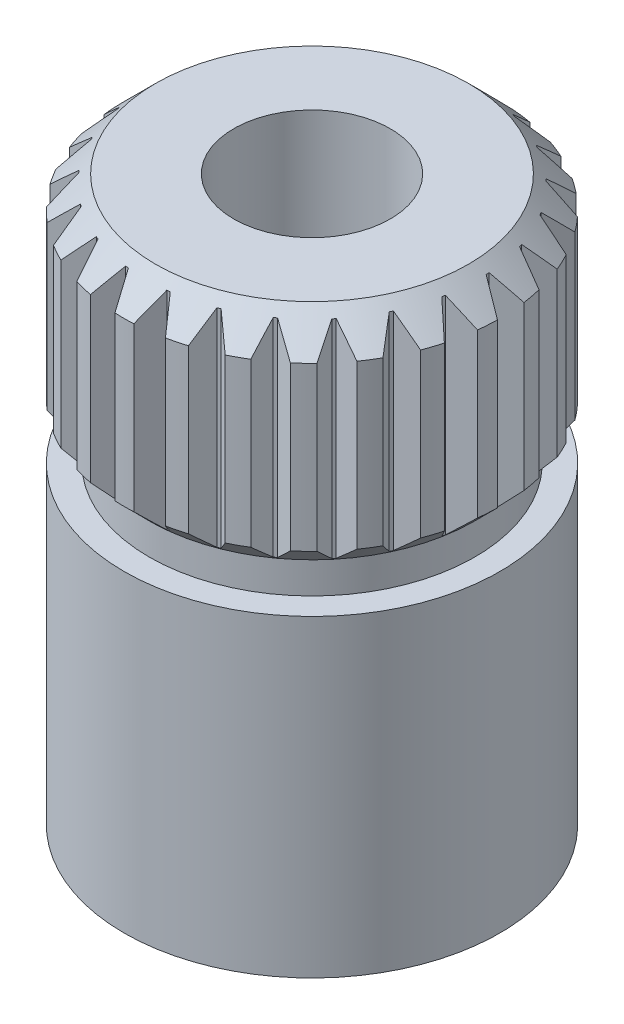
SolidWorks part; units mm, degrees
material "Brass"
ref_plane "Front Plane" through (0, 0, 0) normal (0, 0, 1) x (1, 0, 0)
ref_plane "Top Plane" through (0, 0, 0) normal (0, 1, 0) x (1, 0, 0)
ref_plane "Right Plane" through (0, 0, 0) normal (1, 0, 0) x (0, 0, -1)
sketch "Sketch1" plane through (0, 0, 0) normal (0, 1, 0) x (1, 0, 0)
  circle A0 centre (0, 0) radius 3
  dimension "D1" = 6
extrude "Boss-Extrude1" add sketch "Sketch1" along normal blind 9
sketch "Sketch2" plane through (0, 0, 0) normal (0, 0, 1) x (1, 0, 0)
  line L0 (3, 5) -> (2.6, 5)
  line L1 (2.6, 5) -> (2.6, 5.5)
  line L2 (2.6, 5.5) -> (3, 5.5)
  line L3 (3, 5.5) -> (3, 5)
  line L4 (3, 9) -> (-3, 9) construction
  line L5 (3, 0) -> (3, 9) construction
  dimension "D1" = 4
  dimension "D2" = 0.5
  dimension "D3" = 0.4
ref_axis "Axis1" through (0, 9, 0) along (0, -1, 0)
revolve "Cut-Revolve1" cut sketch "Sketch2" angle 360 about axis through (0, 9, 0) along (0, -1, 0)
chamfer "Chamfer1" distance 0.5 distance2 0.5 1 edges at (0, 9, 3)
sketch "Sketch3" plane through (0, 9, 0) normal (0, 1, 0) x (1, 0, 0)
  circle A0 centre (0, 0) radius 1.25
  dimension "D1" = 2.5
extrude "Cut-Extrude1" cut sketch "Sketch3" against normal through all
cosmetic thread "Cosmetic Thread1" parameters "D2"=3
chamfer "Chamfer2" distance 0.4 angle 45 1 edges at (0, 5.5, 3)
sketch "Sketch4" plane through (0, 5, 0) normal (0, 1, 0) x (1, 0, 0)
  line L0 (0, 0) -> (0, 50000) construction
  line L1 (-0.226, 2.9915) -> (0, 2.6)
  line L2 (0, 2.6) -> (0.226, 2.9915)
  circle A0 centre (0, 0) radius 3 construction
  circle A1 centre (0, 0) radius 2.6 construction
  arc A2 (0.226, 2.9915) -> (-0.226, 2.9915) centre (0, 0) ccw
  dimension "D1" = 60
extrude "Cut-Extrude2" cut sketch "Sketch4" along normal up to next
chamfer "Chamfer3" distance 0.05 distance2 0.05 1 edges at (0, 7.2, -2.6)
pattern_circular "CirPattern1" count 25 over 360 about axis through (0, 9, 0) along (0, -1, 0) of "Cut-Extrude2", "Chamfer3"
